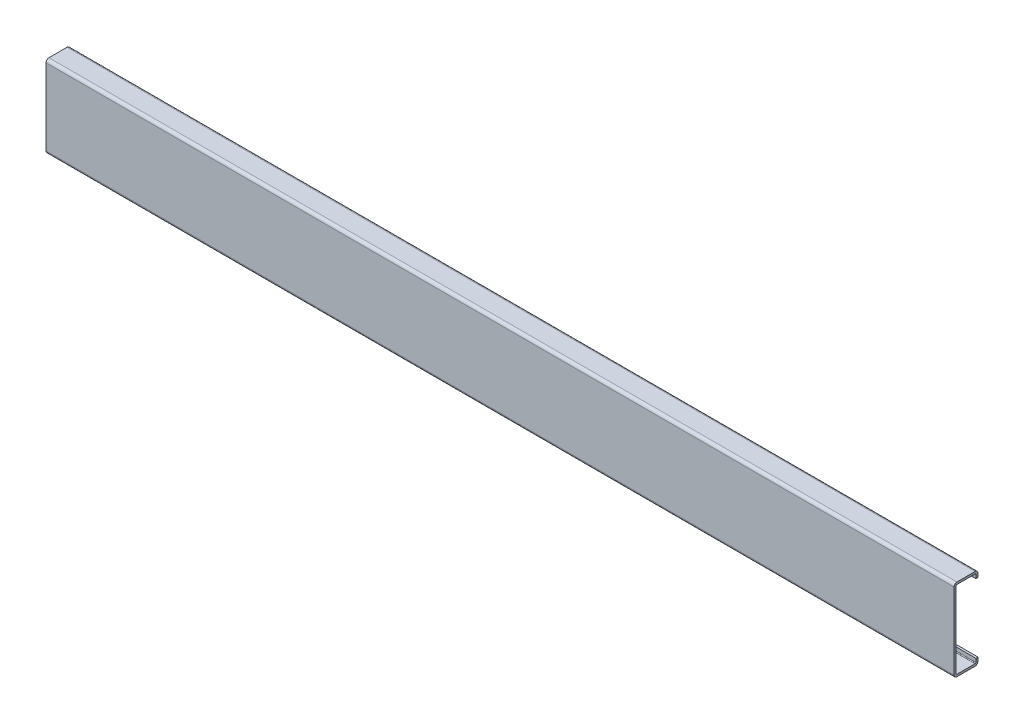
SolidWorks part; units mm, degrees
ref_plane "Спереди" through (0, 0, 0) normal (0, 0, 1) x (1, 0, 0)
ref_plane "Сверху" through (0, 0, 0) normal (0, 1, 0) x (1, 0, 0)
ref_plane "Справа" through (0, 0, 0) normal (1, 0, 0) x (0, 0, -1)
sketch "Эскиз1" plane through (0, 0, 0) normal (1, 0, 0) x (0, 0, -1)
  line L0 (0, -21) -> (0, 21)
  line L1 (-12.4481, 0) -> (26.4522, 0) construction
  line L2 (1, 22) -> (11, 22)
  line L3 (12, 21) -> (12, 19)
  line L4 (12, -21) -> (12, -19)
  line L5 (1, -22) -> (11, -22)
  arc A0 (11, 22) -> (12, 21) centre (11, 21) cw
  arc A1 (0, 21) -> (1, 22) centre (1, 21) cw
  arc A2 (0, -21) -> (1, -22) centre (1, -21) ccw
  arc A3 (11, -22) -> (12, -21) centre (11, -21) ccw
  point P19 (0, 0)
  dimension "D1" = 1
extrude "Вытянуть-Тонкостенный1" add sketch "Эскиз1" along normal blind 500 thin thin type mid plane wall 1.2
